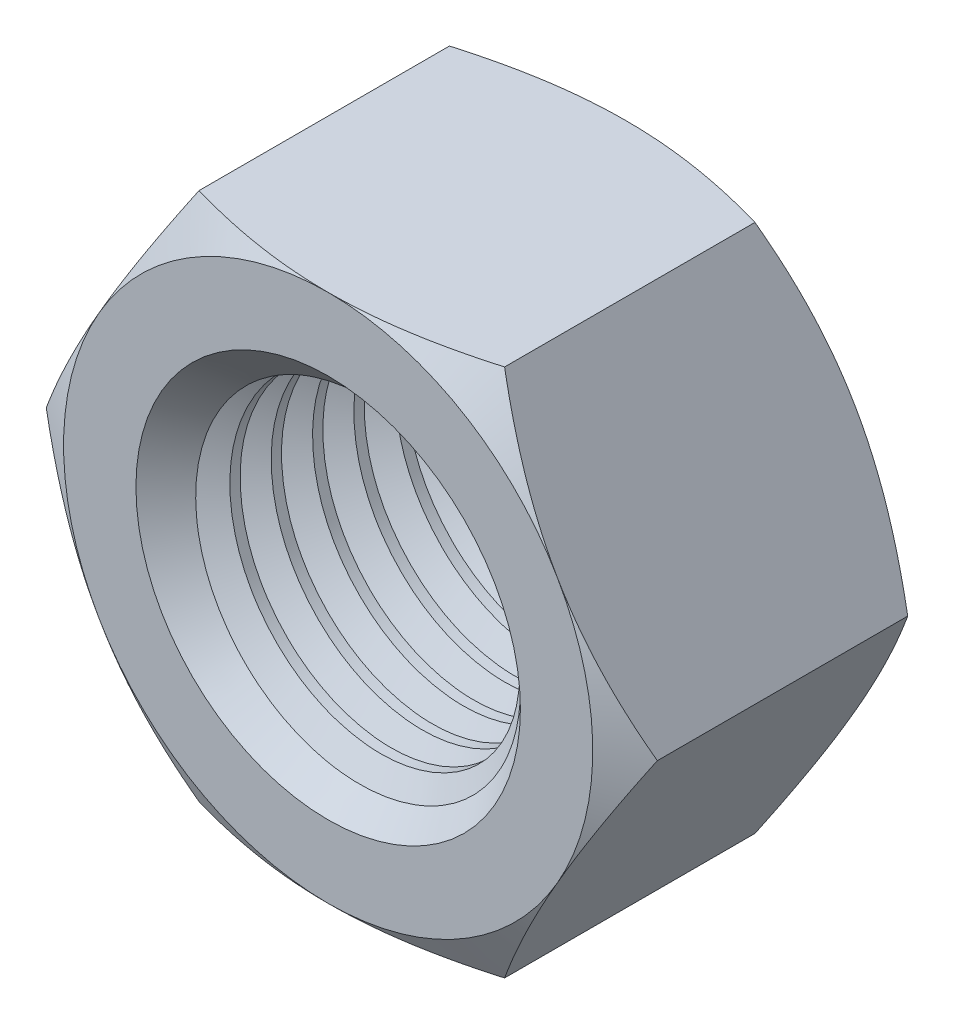
SolidWorks part; units mm, degrees
ref_plane "Front" through (0, 0, 0) normal (0, 0, 1) x (1, 0, 0)
ref_plane "Top" through (0, 0, 0) normal (0, 1, 0) x (1, 0, 0)
ref_plane "Right" through (0, 0, 0) normal (1, 0, 0) x (0, 0, -1)
sketch "Çizim2" plane through (0, 0, 0) normal (0, 0, 1) x (1, 0, 0)
  line L1 (18.4752, 0) -> (9.2376, 16)
  line L2 (9.2376, 16) -> (-9.2376, 16)
  line L3 (-9.2376, 16) -> (-18.4752, 0)
  line L4 (-18.4752, 0) -> (-9.2376, -16)
  line L5 (-9.2376, -16) -> (9.2376, -16)
  line L6 (9.2376, -16) -> (18.4752, 0)
  circle A0 centre (0, 0) radius 16 construction
  point P1 (0, 0)
  dimension "D1" = 32
extrude "Yükseklik-Ekstrüzyon1" add sketch "Çizim2" along normal blind 18
sketch "Çizim3" plane through (0, 0, 18) normal (0, 0, 1) x (1, 0, 0)
  circle A0 centre (0, 0) radius 16
extrude "Kes-Ekstrüzyon1" cut sketch "Çizim3" against normal blind 18 draft 60 flip side to cut
sketch "Çizim4" plane through (0, 0, 0) normal (0, 0, -1) x (-1, 0, 0)
  circle A0 centre (0, 0) radius 16
extrude "Kes-Ekstrüzyon2" cut sketch "Çizim4" against normal blind 18 draft 60 flip side to cut
sketch "Çizim5" plane through (0, 0, 0) normal (0, 0, -1) x (-1, 0, 0)
  circle A0 centre (0, 0) radius 9.375
  dimension "D1" = 18.75
extrude "Kes-Ekstrüzyon3" cut sketch "Çizim5" against normal blind 18 contours A0
chamfer "Pah1" distance 2.25 angle 45 2 edges at (-9.375, 0, 18) (-9.375, 0, 0)
sketch "Çizim6" plane through (0, 0, 18) normal (0, 0, 1) x (1, 0, 0)
  circle A0 centre (0, 0) radius 9.375
curve "Helis/Spiral2" pitch 2.5 height 22 radius 9.375 centre (0, 0, 18) axis (0, 0, -1) start towards (-1, 0, 0)
ref_plane "Düzlem1" through (-2.897, -8.9162, -4) normal (-0.9502, 0.3087, -0.0424) x (-0.0403, 0.0131, 0.9991)
sketch "Çizim7" plane through (-2.897, -8.9162, -4) normal (-0.9502, 0.3087, -0.0424) x (-0.0403, 0.0131, 0.9991)
  line L0 (1.2293, 0.5042) -> (-1.2293, 0.5042)
  line L1 (0, -1.625) -> (1.2293, 0.5042)
  line L3 (-1.2293, 0.5042) -> (0, -1.625)
  line L5 (1.4073, 0.8125) -> (0, 0.8125) [skipped]
  circle A0 centre (0, 0) radius 0.8125 construction
  dimension "D1" = 1.625
sweep "Kes-Süpür1" cut profiles "Çizim7" path "Helis/Spiral2" align with end faces yes
